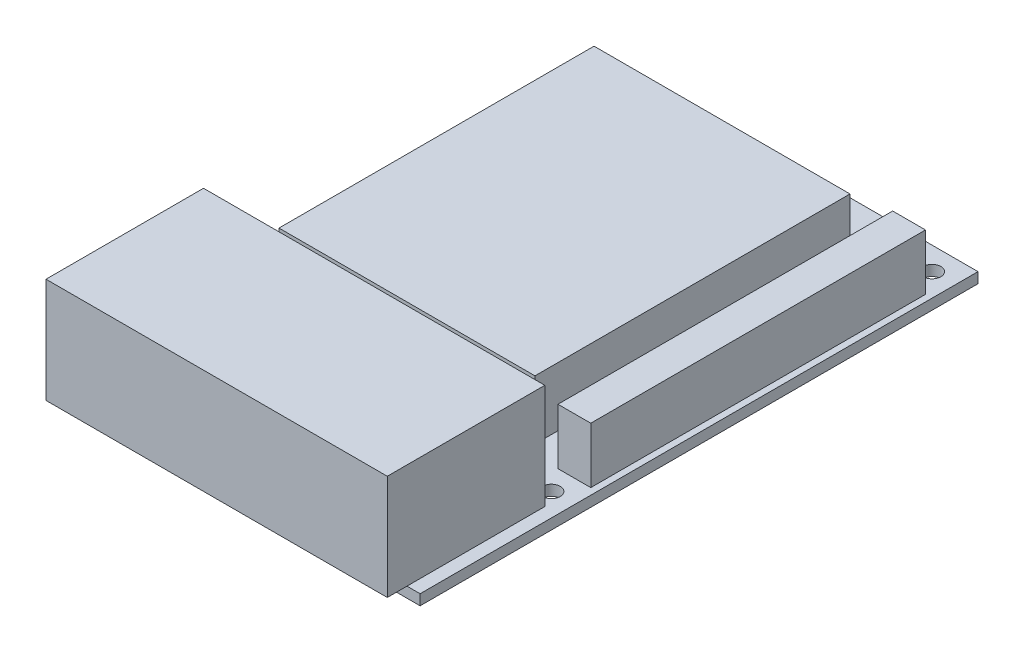
SolidWorks part; units mm, degrees
ref_plane "Front Plane" through (0, 0, 0) normal (0, 0, 1) x (1, 0, 0)
ref_plane "Top Plane" through (0, 0, 0) normal (0, 1, 0) x (1, 0, 0)
ref_plane "Right Plane" through (0, 0, 0) normal (1, 0, 0) x (0, 0, -1)
sketch "SK_Board" plane through (0, 0, 0) normal (0, 1, 0) x (1, 0, 0)
  line L1 (-28, 42.5) -> (28, 42.5)
  line L2 (-28, 42.5) -> (-28, -42.5)
  line L3 (-28, -42.5) -> (28, -42.5)
  line L4 (28, 42.5) -> (28, -42.5)
  dimension "D1" = 85
  dimension "D2" = 56
  dimension "D3" = 42.5
  dimension "D4" = 28
extrude "EX_Board" add sketch "SK_Board" along normal blind 1.6
sketch "SK_MountHoles_4x" plane through (0, 0, 0) normal (0, 1, 0) x (1, 0, 0)
  circle A0 centre (-24.5, 39) radius 1.35
  circle A1 centre (24.5, 39) radius 1.35
  circle A2 centre (-24.5, -19) radius 1.35
  circle A3 centre (24.5, -19) radius 1.35
  dimension "D3" = 2.7
  dimension "D6" = 2.7
  dimension "D9" = 2.7
  dimension "D12" = 2.7
  dimension "D1" = 39
  dimension "D2" = 24.5
  dimension "D4" = 39
  dimension "D5" = 24.5
  dimension "D7" = 19
  dimension "D8" = 24.5
  dimension "D10" = 19
  dimension "D11" = 24.5
extrude "CUT_MountHoles_4x" cut sketch "SK_MountHoles_4x" along normal blind 1.6
ref_plane "PL_Zp1_6" through (0, 1.6, 0) normal (0, 1, 0) x (1, 0, 0)
sketch "SK_Ports_USB_ETH" plane through (0, 1.6, 0) normal (0, 1, 0) x (1, 0, 0)
  line L1 (-26, -21.5) -> (26, -21.5)
  line L2 (-26, -21.5) -> (-26, -45.5)
  line L3 (-26, -45.5) -> (26, -45.5)
  line L4 (26, -21.5) -> (26, -45.5)
  dimension "D1" = 24
  dimension "D2" = 52
  dimension "D3" = 21.5
  dimension "D4" = 26
extrude "EX_Ports_USB_ETH" add sketch "SK_Ports_USB_ETH" along normal blind 16
sketch "SK_ActiveCooler" plane through (0, 1.6, 0) normal (0, 1, 0) x (1, 0, 0)
  line L1 (-22, 34) -> (17, 34)
  line L2 (-22, 34) -> (-22, -14)
  line L3 (-22, -14) -> (17, -14)
  line L4 (17, 34) -> (17, -14)
  dimension "D1" = 48
  dimension "D2" = 39
  dimension "D3" = 34
  dimension "D4" = 22
extrude "EX_ActiveCooler" add sketch "SK_ActiveCooler" along normal blind 9
sketch "SK_GPIO" plane through (0, 1.6, 0) normal (0, 1, 0) x (1, 0, 0)
  line L1 (22, 35.5) -> (27, 35.5)
  line L2 (22, 35.5) -> (22, -15.5)
  line L3 (22, -15.5) -> (27, -15.5)
  line L4 (27, 35.5) -> (27, -15.5)
  dimension "D1" = 51
  dimension "D2" = 5
  dimension "D3" = 35.5
  dimension "D4" = 22
extrude "EX_GPIO" add sketch "SK_GPIO" along normal blind 8.5
ref_axis "AX_X" through (0, 0, -46.9) along (0, 0, 1)
ref_axis "AX_Y" through (30.8, 0, 0) along (-1, 0, 0)
ref_axis "AX_Z" through (0, 18.48, 0) along (0, -1, 0)
